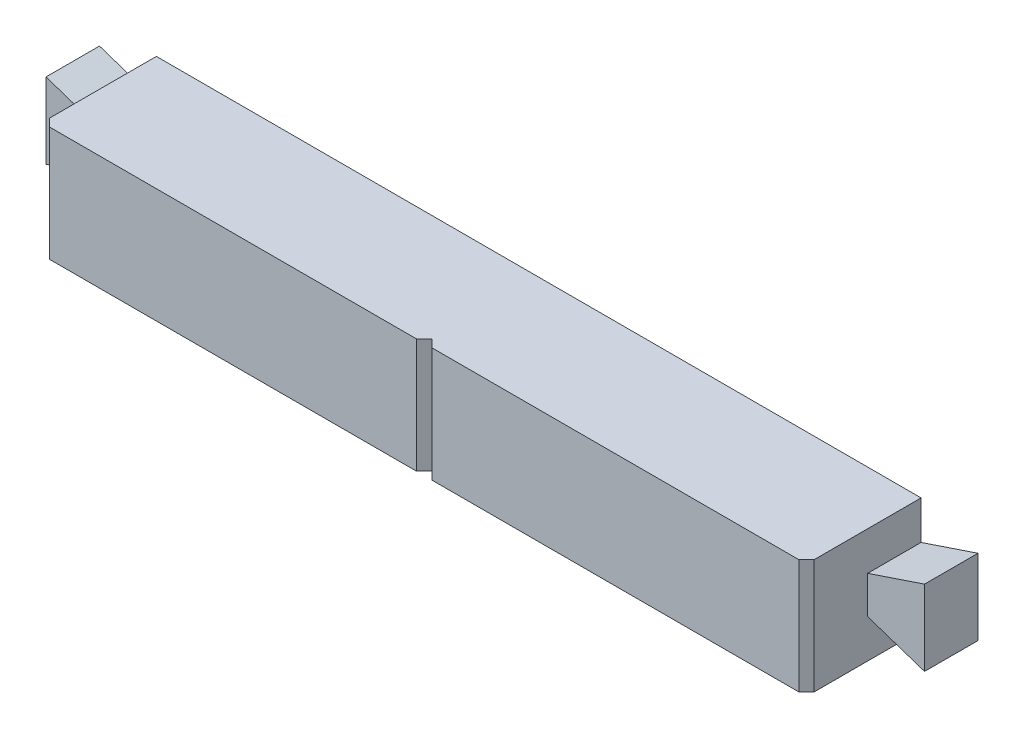
SolidWorks part; units mm, degrees
ref_plane "Front Plane" through (0, 0, 0) normal (0, 0, 1) x (1, 0, 0)
ref_plane "Top Plane" through (0, 0, 0) normal (0, 1, 0) x (1, 0, 0)
ref_plane "Right Plane" through (0, 0, 0) normal (1, 0, 0) x (0, 0, -1)
sketch "Sketch1" plane through (0, 0, 0) normal (0, 0, 1) x (1, 0, 0)
  line L1 (-50.05, -7.5) -> (50.05, -7.5)
  line L2 (-50.05, -7.5) -> (-50.05, 7.5)
  line L3 (-50.05, 7.5) -> (50.05, 7.5)
  line L4 (50.05, -7.5) -> (50.05, 7.5)
  line L5 (-50.05, -7.5) -> (50.05, 7.5) construction
  line L6 (-50.05, 7.5) -> (50.05, -7.5) construction
  point P0 (0, 0)
  dimension "D1" = 100.1
  dimension "D2" = 15
extrude "Boss-Extrude1" add sketch "Sketch1" along normal blind 15
sketch "Sketch2" plane through (0, 0, 0) normal (0, 0, 1) x (1, 0, 0)
  line L0 (-50.05, 0) -> (50.05, 0) construction
  line L1 (-50.05, 7.5) -> (-50.05, -7.5) construction
  line L2 (50.05, -7.5) -> (50.05, 7.5) construction
  line L3 (-50.05, 0) -> (-50.05, 2.45)
  line L4 (-50.05, 2.45) -> (-57.5, 4.95)
  line L6 (-57.5, -4.95) -> (-50.05, -2.45)
  line L7 (-50.05, -2.45) -> (-50.05, 0)
  line L8 (-50.05, 0) -> (-63.3586, 0) construction
  line L9 (-57.5, 4.95) -> (-57.5, 0)
  line L10 (-57.5, 0) -> (-57.5, -4.95)
  line L11 (0, 7.5) -> (0, -7.5) construction
  line L12 (50.05, 7.5) -> (-50.05, 7.5) construction
  line L13 (-50.05, -7.5) -> (50.05, -7.5) construction
  line L14 (50.05, 0) -> (63.3586, 0) construction
  line L15 (57.5, 0) -> (57.5, -4.95)
  line L16 (57.5, 4.95) -> (57.5, 0)
  line L17 (50.05, -2.45) -> (50.05, 0)
  line L18 (57.5, -4.95) -> (50.05, -2.45)
  line L19 (50.05, 2.45) -> (57.5, 4.95)
  line L20 (50.05, 0) -> (50.05, 2.45)
  dimension "D1" = 2.45
  dimension "D2" = 2.45
  dimension "D3" = 4.95
  dimension "D4" = 4.95
  dimension "D5" = 7.45
extrude "Boss-Extrude2" add sketch "Sketch2" along normal blind 7
chamfer "Chamfer1" distance 1 angle 45 2 edges at (-50.05, 0, 15) (50.05, 0, 15)
sketch "Sketch3" plane through (0, -7.5, 0) normal (0, -1, 0) x (1, 0, 0)
  line L0 (-50.05, 5.75) -> (50.05, 5.75) construction
  line L1 (-50.05, 7) -> (-50.05, 0) construction
  line L2 (50.05, 14) -> (50.05, 0) construction
  line L3 (-50.05, 0) -> (50.05, 0) construction
  line L4 (0, 15) -> (0, 0) construction
  line L5 (-49.05, 15) -> (49.05, 15) construction
  circle A0 centre (-25, 5.75) radius 2.5
  circle A1 centre (25, 5.75) radius 2.5
  dimension "D2" = 5
  dimension "D3" = 5
  dimension "D1" = 5.75
  dimension "D4" = 25
  dimension "D5" = 25
extrude "Cut-Extrude1" cut sketch "Sketch3" against normal blind 8
sketch "Sketch4" plane through (0, 0, 15) normal (0, 0, 1) x (1, 0, 0)
  line L0 (0, 7.5) -> (0, -7.5) construction
  line L1 (49.05, 7.5) -> (-49.05, 7.5) construction
  line L2 (-49.05, -7.5) -> (49.05, -7.5) construction
  line L4 (-1, -7.5) -> (1, -7.5)
  line L5 (-1, -7.5) -> (-1, 7.5)
  line L6 (-1, 7.5) -> (1, 7.5)
  line L7 (1, -7.5) -> (1, 7.5)
  line L8 (-1, -7.5) -> (1, 7.5) construction
  line L9 (-1, 7.5) -> (1, -7.5) construction
  point P6 (0, 0)
  dimension "D1" = 2
extrude "Cut-Extrude2" cut sketch "Sketch4" against normal blind 2
chamfer "Chamfer2" distance 2 angle 45 2 edges at (1, 0, 13) (-1, 0, 13)
